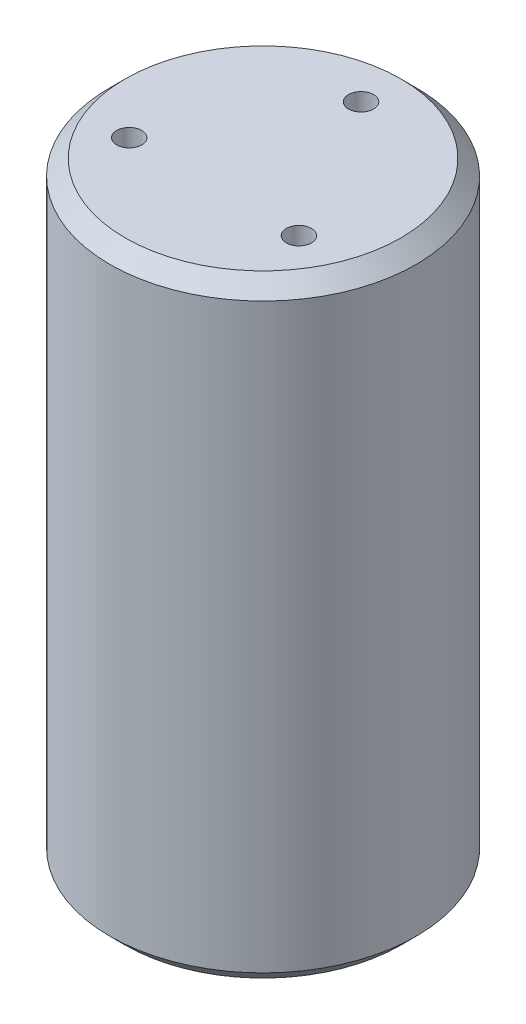
SolidWorks part; units mm, degrees
ref_plane "正面" through (0, 0, 0) normal (0, 0, 1) x (1, 0, 0)
ref_plane "平面" through (0, 0, 0) normal (0, 1, 0) x (1, 0, 0)
ref_plane "右側面" through (0, 0, 0) normal (1, 0, 0) x (0, 0, -1)
sketch "ｽｹｯﾁ1" plane through (0, 0, 0) normal (0, 1, 0) x (1, 0, 0)
  circle A0 centre (0, 0) radius 25
  dimension "D1" = 50
extrude "ﾎﾞｽ - 押し出し1" add sketch "ｽｹｯﾁ1" along normal blind 100
sketch "ｽｹｯﾁ2" plane through (0, 100, 0) normal (0, 1, 0) x (1, 0, 0)
  line L0 (0, 16) -> (0, 0) construction
  line L1 (13.8564, -8) -> (0, 0) construction
  line L2 (-13.8564, -8) -> (0, 0) construction
  circle A0 centre (0, 16) radius 2.05
  circle A1 centre (13.8564, -8) radius 2.05
  circle A2 centre (-13.8564, -8) radius 2.05
  dimension "D1" = 16
  dimension "D2" = 4.1
  dimension "D3" = 3
extrude "ｶｯﾄ - 押し出し1" cut sketch "ｽｹｯﾁ2" against normal blind 5
chamfer "面取り1" distance 2.5 angle 45 2 edges at (0, 0, 25) (0, 100, 25)
sketch "ｽｹｯﾁ3" plane through (0, 0, 0) normal (0, -1, 0) x (1, 0, 0)
  line L0 (0, 0) -> (0, -16) construction
  line L1 (13.8564, 8) -> (0, 0) construction
  line L2 (0, 0) -> (-13.8564, 8) construction
  circle A0 centre (0, -16) radius 2.05
  circle A1 centre (-13.8564, 8) radius 2.05
  circle A2 centre (13.8564, 8) radius 2.05
  dimension "D1" = 16
  dimension "D2" = 4.1
  dimension "D3" = 3
extrude "ｶｯﾄ - 押し出し2" cut sketch "ｽｹｯﾁ3" against normal blind 5
